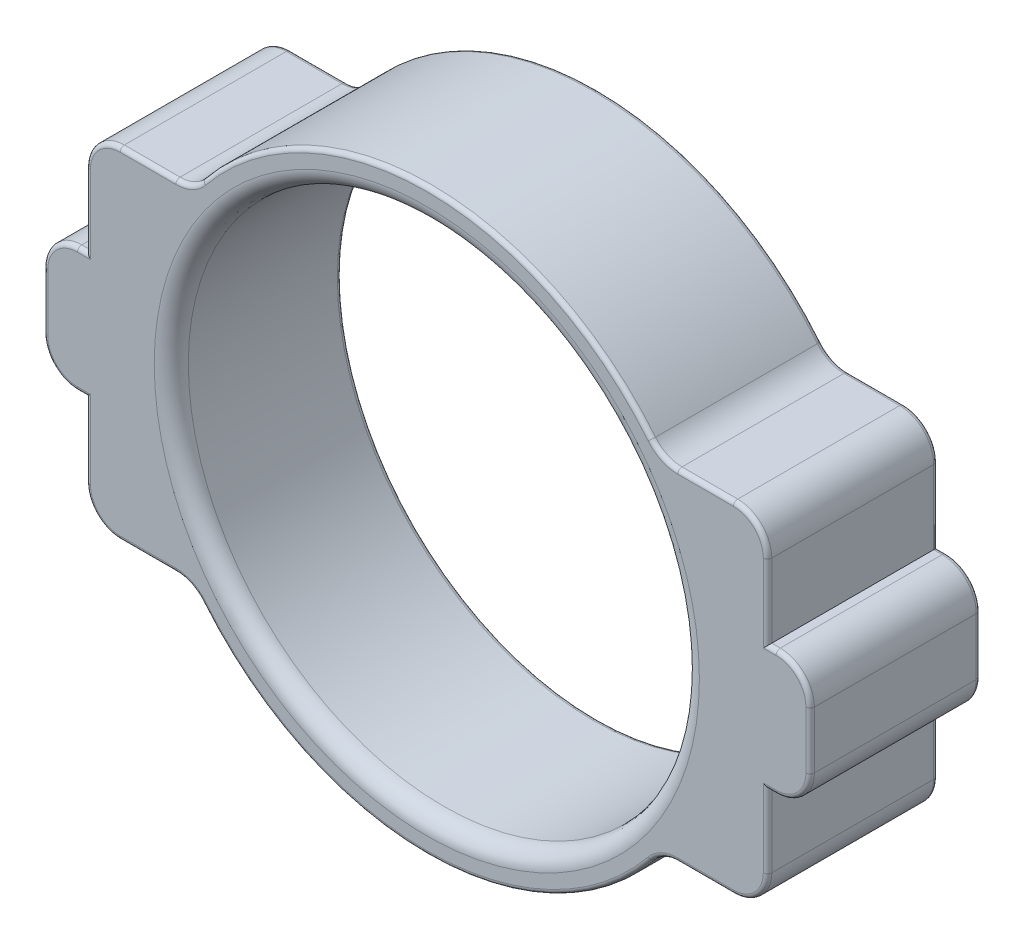
SolidWorks part; units mm, degrees
ref_plane "Plan de face" through (0, 0, 0) normal (0, 0, 1) x (1, 0, 0)
ref_plane "Plan de dessus" through (0, 0, 0) normal (0, 1, 0) x (1, 0, 0)
ref_plane "Plan de droite" through (0, 0, 0) normal (1, 0, 0) x (0, 0, -1)
sketch "Esquisse1" plane through (0, 0, 0) normal (0, 0, 1) x (1, 0, 0)
  line L0 (14.7309, -10) -> (18, -10)
  line L1 (-18, -10) -> (-14.7309, -10)
  line L2 (-20, -8) -> (-20, -3.6739)
  line L3 (-18, 10) -> (-14.7309, 10)
  line L4 (20, -8) -> (20, -3.6739)
  line L5 (-20, -10) -> (20, 10) construction
  line L6 (-20, 10) -> (20, -10) construction
  line L7 (14.7309, 10) -> (18, 10)
  line L8 (-20, 3.6739) -> (-20, 8)
  line L9 (-20.5, -3.6739) -> (-20, -3.6739)
  line L10 (-22.5, -1.6739) -> (-22.5, 1.6739)
  line L11 (-20.5, 3.6739) -> (-20, 3.6739)
  line L12 (22.5, -1.6739) -> (22.5, 1.6739)
  line L13 (-22.5, -3.6739) -> (-20, -3.2657) construction
  line L14 (-22.5, 3.6739) -> (-20, 3.2657) construction
  line L15 (-14.8039, 2.4173) -> (22.5, -3.6739) construction
  line L16 (20, 3.6739) -> (20, 8)
  line L17 (-14.8039, -2.4173) -> (22.5, 3.6739) construction
  line L19 (20, 3.6739) -> (20.5, 3.6739)
  line L20 (20, -3.6739) -> (20.5, -3.6739)
  circle A0 centre (0, 0) radius 15
  arc A1 (-13.1803, -10.7368) -> (13.1803, -10.7368) centre (0, 0) ccw
  arc A2 (13.1803, 10.7368) -> (-13.1803, 10.7368) centre (0, 0) ccw
  arc A3 (20.5, 3.6739) -> (22.5, 1.6739) centre (20.5, 1.6739) cw
  arc A4 (20.5, -3.6739) -> (22.5, -1.6739) centre (20.5, -1.6739) ccw
  arc A5 (-20.5, -3.6739) -> (-22.5, -1.6739) centre (-20.5, -1.6739) cw
  arc A6 (-22.5, 1.6739) -> (-20.5, 3.6739) centre (-20.5, 1.6739) cw
  arc A7 (18, 10) -> (20, 8) centre (18, 8) cw
  arc A8 (18, -10) -> (20, -8) centre (18, -8) ccw
  arc A9 (-18, -10) -> (-20, -8) centre (-18, -8) cw
  arc A10 (-20, 8) -> (-18, 10) centre (-18, 8) cw
  arc A11 (-13.1803, -10.7368) -> (-14.7309, -10) centre (-14.7309, -12) ccw
  arc A12 (13.1803, -10.7368) -> (14.7309, -10) centre (14.7309, -12) cw
  arc A13 (13.1803, 10.7368) -> (14.7309, 10) centre (14.7309, 12) ccw
  arc A14 (-14.7309, 10) -> (-13.1803, 10.7368) centre (-14.7309, 12) ccw
  point P51 (13.7477, -10)
  point P54 (13.7477, 10)
  dimension "D1" = 30
  dimension "D2" = 34
  dimension "D6" = 2
  dimension "D7" = 2
  dimension "D3" = 40
  dimension "D4" = 20
  dimension "D5" = 45
sketch "Esquisse2" plane through (0, 0, 0) normal (0, 0, 1) x (1, 0, 0)
  line L0 (0, 0) -> (0, 18.9624) construction
  line L1 (-17.9552, -8.7273) -> (-16.8059, -8.7273)
  line L2 (-18.9552, -7.7273) -> (-18.9552, -3.7979)
  line L3 (-17.9552, 8.7273) -> (-16.8059, 8.7273)
  line L4 (-15.8059, -7.7273) -> (-15.8059, 7.7273)
  line L5 (-18.9552, -8.7273) -> (-15.8059, 8.7273) construction
  line L6 (-18.9552, 8.7273) -> (-15.8059, -8.7273) construction
  line L7 (-18.9552, 3.7979) -> (-18.9552, 7.7273)
  line L8 (-20.7842, -2.7979) -> (-19.9552, -2.7979)
  line L9 (-21.7842, -1.7979) -> (-21.7842, 1.7979)
  line L10 (-20.7842, 2.7979) -> (-19.9552, 2.7979)
  line L12 (-21.7842, -2.7979) -> (-18.7005, 2.7979) construction
  line L13 (-21.7842, 2.7979) -> (-18.7005, -2.7979) construction
  line L14 (17.9552, -8.7273) -> (16.8059, -8.7273)
  line L15 (18.9552, -7.7273) -> (18.9552, -3.7979)
  line L16 (20.7842, -2.7979) -> (19.9552, -2.7979)
  line L17 (21.7842, -1.7979) -> (21.7842, 1.7979)
  line L18 (20.7842, 2.7979) -> (19.9552, 2.7979)
  line L19 (18.9552, 3.7979) -> (18.9552, 7.7273)
  line L20 (17.9552, 8.7273) -> (16.8059, 8.7273)
  line L21 (15.8059, -7.7273) -> (15.8059, 7.7273)
  arc A0 (-17.9552, -8.7273) -> (-18.9552, -7.7273) centre (-17.9552, -7.7273) cw
  arc A1 (-16.8059, -8.7273) -> (-15.8059, -7.7273) centre (-16.8059, -7.7273) ccw
  arc A2 (-16.8059, 8.7273) -> (-15.8059, 7.7273) centre (-16.8059, 7.7273) cw
  arc A3 (-18.9552, 7.7273) -> (-17.9552, 8.7273) centre (-17.9552, 7.7273) cw
  arc A4 (-21.7842, 1.7979) -> (-20.7842, 2.7979) centre (-20.7842, 1.7979) cw
  arc A5 (-20.7842, -2.7979) -> (-21.7842, -1.7979) centre (-20.7842, -1.7979) cw
  arc A6 (-18.9552, -3.7979) -> (-19.9552, -2.7979) centre (-19.9552, -3.7979) ccw
  arc A7 (-19.9552, 2.7979) -> (-18.9552, 3.7979) centre (-19.9552, 3.7979) ccw
  arc A8 (16.8059, -8.7273) -> (15.8059, -7.7273) centre (16.8059, -7.7273) cw
  arc A9 (17.9552, -8.7273) -> (18.9552, -7.7273) centre (17.9552, -7.7273) ccw
  arc A10 (18.9552, -3.7979) -> (19.9552, -2.7979) centre (19.9552, -3.7979) cw
  arc A11 (20.7842, -2.7979) -> (21.7842, -1.7979) centre (20.7842, -1.7979) ccw
  arc A12 (21.7842, 1.7979) -> (20.7842, 2.7979) centre (20.7842, 1.7979) ccw
  arc A13 (19.9552, 2.7979) -> (18.9552, 3.7979) centre (19.9552, 3.7979) cw
  arc A14 (18.9552, 7.7273) -> (17.9552, 8.7273) centre (17.9552, 7.7273) ccw
  arc A15 (16.8059, 8.7273) -> (15.8059, 7.7273) centre (16.8059, 7.7273) ccw
  point P0 (-17.3806, 0)
  point P20 (-20.2424, 0)
  dimension "D1" = 1
  dimension "D2" = 1
  dimension "D3" = 1
extrude "Boss.-Extru.2" add sketch "Esquisse1" along normal blind 5 and the other way blind 5
extrude "Enlèv. mat.-Extru.1" cut sketch "Esquisse2" against normal blind 4 and the other way blind 4
fillet "Congé1" radius 1 1 edges at (15, 0, 5)
fillet "Congé2" radius 0.25 1 edges at (15, 0, -5)
fillet "Congé3" radius 0.25 36 edges at (20, 5.8369, -5) (19.4142, 9.4142, -5) (16.3655, 10, -5) (13.8725, 10.1936, -5) (0, 17, -5) (-20, 5.8369, -5) (-19.4142, 9.4142, -5) (-16.3655, 10, -5) (-20, -5.8369, -5) (-19.4142, -9.4142, -5) (-16.3655, -10, -5) (20, -5.8369, -5) (19.4142, -9.4142, -5) (16.3655, -10, -5) (13.8725, -10.1936, -5) (0, -17, -5) (20, 5.8369, 5) (19.4142, 9.4142, 5) (16.3655, 10, 5) (13.8725, 10.1936, 5) (0, 17, 5) (-20, 5.8369, 5) (-19.4142, 9.4142, 5) (-16.3655, 10, 5) (-20, -5.8369, 5) (-19.4142, -9.4142, 5) (-16.3655, -10, 5) (20, -5.8369, 5) (19.4142, -9.4142, 5) (16.3655, -10, 5) (13.8725, -10.1936, 5) (0, -17, 5) (-13.8725, 10.1936, -5) (-13.8725, -10.1936, -5) (-13.8725, 10.1936, 5) (-13.8725, -10.1936, 5)
fillet "Congé4" radius 0.25 20 edges at (-20.125, 3.6739, -5) (-20.125, -3.6739, -5) (-21.9142, -3.0881, -5) (-22.5, 0, -5) (20.125, -3.6739, -5) (21.9142, -3.0881, -5) (22.5, 0, -5) (20.125, 3.6739, -5) (-20.125, 3.6739, 5) (-20.125, -3.6739, 5) (-21.9142, -3.0881, 5) (-22.5, 0, 5) (20.125, -3.6739, 5) (21.9142, -3.0881, 5) (22.5, 0, 5) (20.125, 3.6739, 5) (-21.9142, 3.0881, -5) (21.9142, 3.0881, -5) (-21.9142, 3.0881, 5) (21.9142, 3.0881, 5)
